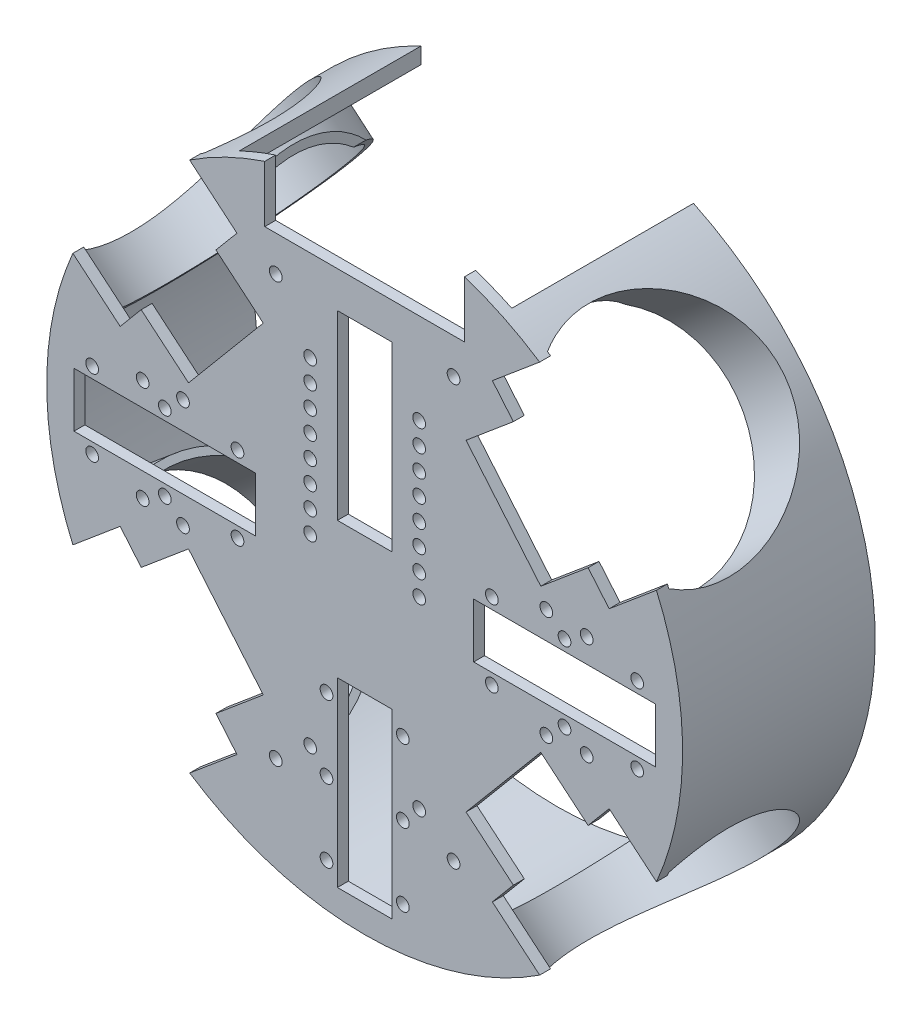
SolidWorks part; units mm, degrees
ref_plane "Front Plane" through (0, 0, 0) normal (0, 0, 1) x (1, 0, 0)
ref_plane "Top Plane" through (0, 0, 0) normal (0, 1, 0) x (1, 0, 0)
ref_plane "Right Plane" through (0, 0, 0) normal (1, 0, 0) x (0, 0, -1)
sketch "Sketch1" plane through (0, 0, 0) normal (0, 0, 1) x (1, 0, 0)
  circle A1 centre (0, 0) radius 87.5
  dimension "D1" = 87.5
extrude "Boss-Extrude1" add sketch "Sketch1" against normal blind 3
sketch "Sketch3" plane through (0, 0, 0) normal (0, 0, 1) x (1, 0, 0)
  line L0 (-87.5, 0) -> (0, 0) construction
  line L1 (0, 0) -> (-38.1893, 32.0446) construction
  line L2 (-48.4739, 19.7879) -> (-27.9047, 44.3013)
  line L3 (-48.4739, 19.7879) -> (-61.4966, 30.7153)
  line L4 (-61.4966, 30.7153) -> (-67.2817, 23.8209)
  line L5 (-67.2817, 23.8209) -> (-80.3045, 34.7483)
  line L6 (-80.3045, 34.7483) -> (-48.1651, 73.0505) construction
  line L7 (-48.1651, 73.0505) -> (-35.1423, 62.1231)
  line L8 (-35.1423, 62.1231) -> (-40.9274, 55.2287)
  line L9 (-40.9274, 55.2287) -> (-27.9047, 44.3013)
  line L10 (-61.4966, 30.7153) -> (-40.9274, 55.2287) construction
  line L11 (-38.1893, 32.0446) -> (-51.212, 42.972) construction
  line L12 (-51.212, 42.972) -> (-64.2348, 53.8994) construction
  line L13 (-61.105, 14.0691) -> (-24.4661, 57.7336) construction
  circle A0 centre (0, 0) radius 87.5 construction
  arc A1 (-48.1651, 73.0505) -> (-80.3045, 34.7483) centre (0, 0) ccw
  arc A2 (-87.5, 0) -> (87.5, 0) centre (0, 0) ccw
  circle A3 centre (-61.105, 14.0691) radius 1.75
  circle A4 centre (-24.4661, 57.7336) radius 1.75
  point P19 (-42.7855, 35.9013)
  circle M14 centre (0, 0) radius 87.5
  dimension "D8" = 3.5
  dimension "D1" = 40
  dimension "D2" = 32
  dimension "D3" = 50
  dimension "D4" = 17
  dimension "D5" = 17
  dimension "D6" = 57
  dimension "D7" = 6
extrude "Cut-Extrude1" cut sketch "Sketch3" against normal through all contours L9 L8 L7 L5 L4 L3 L2 M14 | A3 | A4 region at (-53.6652, 45.0304, 0)
mirror "Mirror1" about plane through (0, 0, 0) normal (1, 0, 0) of "Cut-Extrude1" second plane through (0, 0, 0) second plane normal (0, 1, 0)
sketch "Sketch4" plane through (0, 0, 0) normal (0, 0, 1) x (1, 0, 0)
  line L1 (-27.5, 107.5) -> (27.5, 107.5)
  line L2 (-27.5, 107.5) -> (-27.5, 67.5)
  line L3 (-27.5, 67.5) -> (27.5, 67.5)
  line L4 (27.5, 107.5) -> (27.5, 67.5)
  line L5 (-27.5, 107.5) -> (27.5, 67.5) construction
  line L6 (-27.5, 67.5) -> (27.5, 107.5) construction
  arc A0 (48.1651, 73.0505) -> (-48.1651, 73.0505) centre (0, 0) ccw construction
  point P0 (0, 87.5)
  dimension "D1" = 55
  dimension "D2" = 40
extrude "Cut-Extrude2" cut sketch "Sketch4" against normal through all and the other way through all
sketch "Sketch5" plane through (0, 0, 0) normal (0, 0, 1) x (1, 0, 0)
  line L0 (0, 0) -> (-50, 0) construction
  line L1 (-50, 15) -> (-50, -15) construction
  circle A0 centre (-50, 15) radius 1.75
  circle A1 centre (-50, -15) radius 1.75
  dimension "D1" = 3.5
  dimension "D2" = 30
  dimension "D3" = 50
extrude "Cut-Extrude3" cut sketch "Sketch5" against normal through all
sketch "Sketch8" plane through (0, 0, 0) normal (0, 0, 1) x (1, 0, 0)
  line L0 (-30, 0) -> (0, 0) construction
  line L1 (-80, 7.5) -> (-30, 7.5)
  line L2 (-80, 7.5) -> (-80, -7.5)
  line L3 (-80, -7.5) -> (-30, -7.5)
  line L4 (-30, 7.5) -> (-30, -7.5)
  line L5 (-80, 7.5) -> (-30, -7.5) construction
  line L6 (-80, -7.5) -> (-30, 7.5) construction
  point P0 (-55, 0)
  dimension "D1" = 30
  dimension "D2" = 50
  dimension "D3" = 15
extrude "Cut-Extrude4" cut sketch "Sketch8" against normal through all
sketch "Sketch9" plane through (0, 0, 0) normal (0, 0, 1) x (1, 0, 0)
  line L0 (-35, 10.5) -> (-35, -10.5) construction
  line L1 (-35, 0) -> (-30, 0) construction
  line L2 (-30, -7.5) -> (-30, 7.5) construction
  circle A0 centre (-35, 10.5) radius 1.75
  circle A1 centre (-35, -10.5) radius 1.75
  circle A2 centre (-55, 10.5) radius 1.75
  circle A3 centre (-55, -10.5) radius 1.75
  circle A4 centre (-75, 10.5) radius 1.75
  circle A5 centre (-75, -10.5) radius 1.75
  dimension "D2" = 3.5
  dimension "D1" = 21
  dimension "D3" = 5
  dimension "D5" = 20
  dimension "D4" = 3
extrude "Cut-Extrude5" cut sketch "Sketch9" against normal through all
pattern_circular "CirPattern1" count 3 every 90 about axis through (0, 0, 0) along (0, 0, 1) of "Cut-Extrude3", "Cut-Extrude4", "Cut-Extrude5"
sketch "Sketch10" plane through (0, 0, 0) normal (0, 0, 1) x (1, 0, 0)
  line L0 (0, 7.5) -> (0, 0) construction
  line L1 (-7.5, 57.5) -> (7.5, 57.5)
  line L2 (-7.5, 57.5) -> (-7.5, 7.5)
  line L3 (-7.5, 7.5) -> (7.5, 7.5)
  line L4 (7.5, 57.5) -> (7.5, 7.5)
  line L5 (-7.5, 57.5) -> (7.5, 7.5) construction
  line L6 (-7.5, 7.5) -> (7.5, 57.5) construction
  line L7 (-27.5, 67.5) -> (27.5, 67.5) construction
  point P0 (0, 32.5)
  dimension "D1" = 15
  dimension "D2" = 50
  dimension "D3" = 10
extrude "Cut-Extrude6" cut sketch "Sketch10" against normal through all
sketch "Sketch11" plane through (0, 0, 0) normal (0, 0, 1) x (1, 0, 0)
  line L0 (-15, 42.5) -> (15, 42.5) construction
  line L1 (0, 42.5) -> (0, 7.5) construction
  line L2 (-7.5, 7.5) -> (7.5, 7.5) construction
  line L3 (-27.5, 67.5) -> (27.5, 67.5) construction
  circle A0 centre (-15, 42.5) radius 1.75
  circle A1 centre (15, 42.5) radius 1.75
  circle A2 centre (-15, 36.5) radius 1.75
  circle A3 centre (15, 36.5) radius 1.75
  circle A4 centre (-15, 30.5) radius 1.75
  circle A5 centre (15, 30.5) radius 1.75
  circle A6 centre (-15, 24.5) radius 1.75
  circle A7 centre (15, 24.5) radius 1.75
  circle A8 centre (-15, 18.5) radius 1.75
  circle A9 centre (15, 18.5) radius 1.75
  circle A10 centre (-15, 12.5) radius 1.75
  circle A11 centre (15, 12.5) radius 1.75
  circle A12 centre (-15, 6.5) radius 1.75
  circle A13 centre (15, 6.5) radius 1.75
  circle A14 centre (-15, 0.5) radius 1.75
  circle A15 centre (15, 0.5) radius 1.75
  dimension "D3" = 3.5
  dimension "D1" = 30
  dimension "D2" = 25
  dimension "D4" = 8
extrude "Cut-Extrude7" cut sketch "Sketch11" against normal through all
sketch "Sketch14" plane through (0, 0, -3) normal (0, 0, 1) x (1, 0, 0)
  circle A0 centre (0, 0) radius 87.5
  circle A1 centre (0, 0) radius 83.5
  dimension "D1" = 4
extrude "Boss-Extrude2" add sketch "Sketch14" against normal blind 50
sketch "Sketch16" plane through (0, 0, 0) normal (0, 1, 0) x (1, 0, 0)
  line L0 (0, 0) -> (0, 53)
  line L1 (87.5, 53) -> (-87.5, 53) construction
ref_plane "Plane1" through (0, 0, 0) normal (0.766, 0.6428, 0) x (0, 0, -1)
sketch "Sketch17" plane through (0, 0, 0) normal (0.766, 0.6428, 0) x (0, 0, -1)
  line L0 (0, 0) -> (53, 0) construction
  line L1 (3, 25.9808) -> (3, -25.9808)
  line L3 (3, -16) -> (3, 16) construction
  arc A0 (3, -25.9808) -> (3, 25.9808) centre (18, 0) ccw
  dimension "D2" = 60
  dimension "D1" = 18
extrude "Cut-Extrude10" cut sketch "Sketch17" against normal through all
ref_plane "Plane2" through (-53.6231, -44.9951, 0) normal (0.766, 0.6428, 0) x (0, 0, -1)
sketch "Sketch18" plane through (-53.6231, -44.9951, 0) normal (0.766, 0.6428, 0) x (0, 0, -1)
  line L1 (3, 25.9808) -> (3, 28.2666)
  line L2 (3, -25.9808) -> (3, -28.2666)
  arc A0 (3, -25.9808) -> (3, 25.9808) centre (18, 0) ccw construction
  arc A1 (3, -25.9808) -> (3, 25.9808) centre (18, 0) ccw
  arc A2 (3, -28.2666) -> (3, 28.2666) centre (18, 0) ccw
  arc A3 (0.5455, -26.8205) -> (2, 27.7128) centre (18, 0) ccw construction
  arc A4 (1.6364, -25.1442) -> (3, 25.9808) centre (18, 0) ccw construction
  dimension "D1" = 2
extrude "Boss-Extrude5" add sketch "Sketch18" against normal up to next
mirror "Mirror3" about plane through (0, 0, 0) normal (1, 0, 0) of "Boss-Extrude5", "Cut-Extrude10" second plane through (0, 0, 0) second plane normal (0, 1, 0)
sketch "Sketch19" plane through (0, 0, -53) normal (0, 0, -1) x (-1, 0, 0)
  line L0 (0, 50.2183) -> (0, 0) construction
  line L1 (-37.5, 124.7817) -> (37.5, 124.7817)
  line L2 (-37.5, 124.7817) -> (-37.5, 50.2183)
  line L3 (-37.5, 50.2183) -> (37.5, 50.2183)
  line L4 (37.5, 124.7817) -> (37.5, 50.2183)
  line L5 (-37.5, 124.7817) -> (37.5, 50.2183) construction
  line L6 (-37.5, 50.2183) -> (37.5, 124.7817) construction
  circle A0 centre (0, 0) radius 87.5 construction
  point P0 (0, 87.5)
  dimension "D1" = 75
extrude "Cut-Extrude11" cut sketch "Sketch19" against normal up to surface (50 mm away) up to face at (0, 4.1476, -3)
